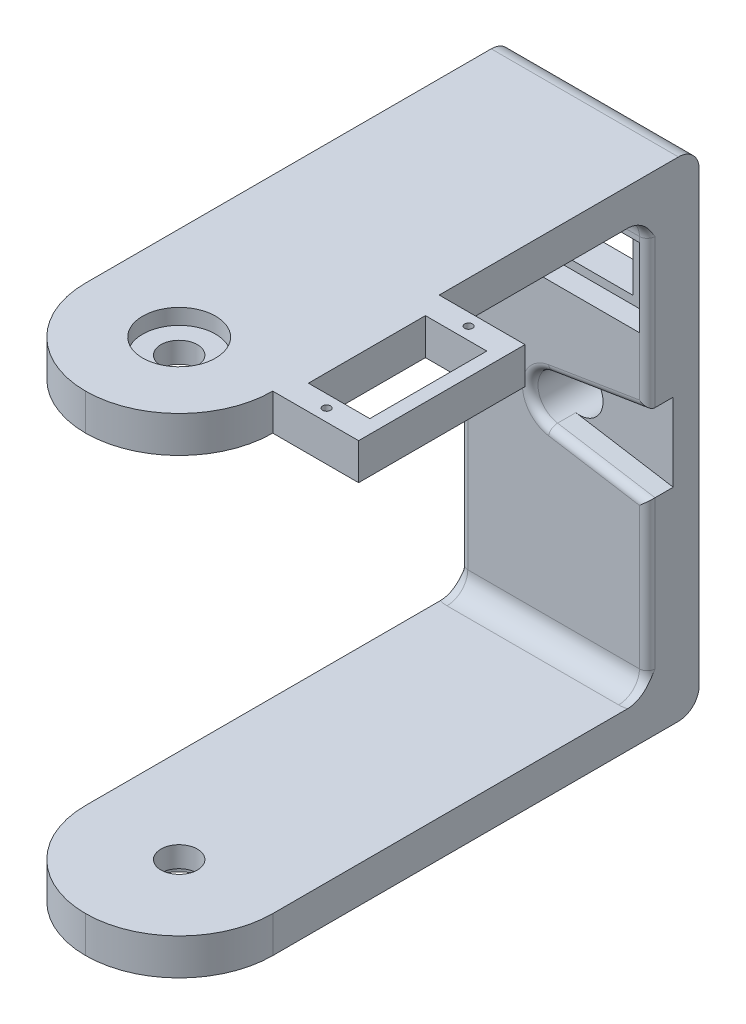
SolidWorks part; units mm, degrees
ref_plane "Front Plane" through (0, 0, 0) normal (1, 0, 0) x (0, 1, 0)
ref_plane "Top Plane" through (0, 0, 0) normal (0, 0, 1) x (0, 1, 0)
ref_plane "Right Plane" through (0, 0, 0) normal (0, 1, 0) x (-1, 0, 0)
sketch "Sketch1" plane through (0, 0, 0) normal (0, 0, 1) x (0, 1, 0)
  line L1 (-47, -18) -> (47, -18)
  line L2 (-47, -18) -> (-47, 18)
  line L3 (-47, 18) -> (47, 18)
  line L4 (47, -18) -> (47, 18)
  line L5 (-47, -18) -> (47, 18) construction
  line L6 (-47, 18) -> (47, -18) construction
  point P0 (0, 0)
  dimension "D1" = 94
  dimension "D2" = 36
extrude "Boss-Extrude1" add sketch "Sketch1" along normal blind 10
sketch "Sketch2" plane through (0, 0, 10) normal (0, 0, 1) x (1, 0, 0)
  line L0 (18, -47) -> (18, 47) construction
  line L1 (-18, 47) -> (18, 47)
  line L2 (-18, 47) -> (-18, 40)
  line L3 (-18, 40) -> (18, 40)
  line L4 (18, 47) -> (18, 40)
  line L6 (-18, -47) -> (18, -47)
  line L7 (-18, -47) -> (-18, -40)
  line L8 (-18, -40) -> (18, -40)
  line L9 (18, -47) -> (18, -40)
  dimension "D1" = 7
extrude "Boss-Extrude2" add sketch "Sketch2" along normal blind 90
sketch "Sketch3" plane through (0, -47, 0) normal (0, -1, 0) x (1, 0, 0)
  line L0 (-18, 82) -> (18, 82) construction
  line L1 (-18, 100) -> (-18, 0) construction
  line L2 (18, 100) -> (18, 0) construction
  line L3 (-18, 100) -> (18, 100) construction
  circle A0 centre (0, 82) radius 3.5
  dimension "D2" = 7
  dimension "D1" = 18
extrude "Cut-Extrude1" cut sketch "Sketch3" against normal through all both and the other way through all
sketch "Sketch4" plane through (0, -47, 0) normal (0, -1, 0) x (1, 0, 0)
  circle A0 centre (0, 82) radius 7
  dimension "D1" = 14
extrude "Cut-Extrude2" cut sketch "Sketch4" against normal blind 3 and the other way through all
sketch "Sketch5" plane through (0, 47, 0) normal (0, 1, 0) x (-1, 0, 0)
  circle A0 centre (0, 82) radius 7
  dimension "D1" = 14
extrude "Cut-Extrude3" cut sketch "Sketch5" against normal blind 3
fillet "Fillet1" radius 18 4 edges at (18, -43.5, 100) (-18, -43.5, 100) (18, 43.5, 100) (-18, 43.5, 100)
sketch "Sketch6" plane through (0, 0, 0) normal (0, 0, -1) x (1, 0, 0)
  circle A0 centre (0, 0) radius 7.5
  dimension "D1" = 15
extrude "Boss-Extrude3" add sketch "Sketch6" along normal blind 8
sketch "Sketch7" plane through (0, 0, -8) normal (0, 0, -1) x (1, 0, 0)
  circle A0 centre (0, 0) radius 4.5
  dimension "D1" = 9
extrude "Cut-Extrude4" cut sketch "Sketch7" against normal through all
fillet "Fillet2" radius 2 1 edges at (-7.5, 0, 0)
sketch "Sketch9" plane through (0, 0, 10) normal (0, 0, 1) x (1, 0, 0)
  line L0 (0, 0) -> (0, 40) construction
  line L1 (0, 27.4841) -> (18, 27.4841) construction
  line L2 (-11.25, 21.5841) -> (11.25, 21.5841)
  line L3 (-11.25, 21.5841) -> (-11.25, 33.3841)
  line L4 (-11.25, 33.3841) -> (11.25, 33.3841)
  line L5 (11.25, 21.5841) -> (11.25, 33.3841)
  line L6 (-11.25, 21.5841) -> (11.25, 33.3841) construction
  line L7 (-11.25, 33.3841) -> (11.25, 21.5841) construction
  line L8 (18, -40) -> (18, 40) construction
  line L9 (0, 27.4841) -> (-18, 27.4841) construction
  line L10 (-18, 40) -> (-18, -40) construction
  circle A1 centre (-13.65, 27.4841) radius 0.75
  circle A2 centre (13.65, 27.4841) radius 0.75
  circle A3 centre (-5.35, 27.4841) radius 5.9 construction
  point P4 (0, 27.4841)
  dimension "D5" = 1.5
  dimension "D1" = 22.5
  dimension "D2" = 11.8
  dimension "D3" = 28
  dimension "D4" = 13.65
  dimension "D6" = 13.65
extrude "Cut-Extrude5" cut sketch "Sketch9" against normal through all
sketch "Sketch10" plane through (0, 0, 10) normal (0, 0, 1) x (1, 0, 0)
  line L0 (-11.25, 27.4841) -> (11.25, 27.4841) construction
  line L1 (-11.25, 33.3841) -> (-11.25, 21.5841) construction
  line L2 (11.25, 21.5841) -> (11.25, 33.3841) construction
  line L4 (-16.5, 19.9841) -> (16.5, 19.9841)
  line L5 (-16.5, 19.9841) -> (-16.5, 34.9841)
  line L6 (-16.5, 34.9841) -> (16.5, 34.9841)
  line L7 (16.5, 19.9841) -> (16.5, 34.9841)
  line L8 (-16.5, 19.9841) -> (16.5, 34.9841) construction
  line L9 (-16.5, 34.9841) -> (16.5, 19.9841) construction
  point P6 (0, 27.4841)
  dimension "D1" = 15
  dimension "D2" = 33
extrude "Cut-Extrude6" cut sketch "Sketch10" against normal offset from surface (4 mm away) 6 up to face at (12.9, 27.4841, 0)
sketch "Sketch11" plane through (0, 47, 0) normal (0, 1, 0) x (-1, 0, 0)
  line L0 (-18, 82) -> (0, 82) construction
  line L1 (-26.0036, 82) -> (-26.0036, 50) construction
  line L2 (-17.5036, 82) -> (-34.5036, 82)
  line L3 (-17.5036, 82) -> (-17.5036, 50)
  line L4 (-17.5036, 50) -> (-34.5036, 50)
  line L5 (-34.5036, 82) -> (-34.5036, 50)
  line L6 (-34.5036, 66) -> (-26.0036, 66) construction
  line L7 (-31.9036, 54.75) -> (-20.1036, 54.75) construction
  line L8 (-31.9036, 54.75) -> (-31.9036, 77.25) construction
  line L9 (-31.9036, 77.25) -> (-20.1036, 77.25) construction
  line L10 (-20.1036, 54.75) -> (-20.1036, 77.25) construction
  line L11 (-31.9036, 54.75) -> (-20.1036, 77.25) construction
  line L12 (-31.9036, 77.25) -> (-20.1036, 54.75) construction
  circle A1 centre (-26.0036, 71.35) radius 5.9 construction
  circle A2 centre (0, 82) radius 21 construction
  circle A3 centre (-26.0036, 71.35) radius 7.1 construction
  point P10 (-26.0036, 66)
  dimension "D6" = 42
  dimension "D5" = 14.2
  dimension "D1" = 17
  dimension "D2" = 32
  dimension "D3" = 11.8
  dimension "D4" = 22.5
extrude "Boss-Extrude4" add sketch "Sketch11" against normal blind 7
sketch "Sketch12" plane through (0, 47, 0) normal (0, 1, 0) x (-1, 0, 0)
  line L0 (-34.5036, 66) -> (18, 66) construction
  line L1 (-34.5036, 82) -> (-34.5036, 50) construction
  line L2 (18, 82) -> (18, 0) construction
  line L3 (-18, 82) -> (-34.5036, 82) construction
  line L4 (-34.5036, 50) -> (-17.5036, 50) construction
  line L5 (-34.5036, 50) -> (-34.5036, 82) construction
  line L6 (-34.5036, 82) -> (-17.5036, 82) construction
  line L7 (-17.5036, 50) -> (-17.5036, 82) construction
  line L8 (-34.5036, 50) -> (-17.5036, 82) construction
  line L9 (-34.5036, 82) -> (-17.5036, 50) construction
  line L10 (-26.0036, 82) -> (-26.0036, 66) construction
  line L11 (-31.9036, 54.75) -> (-20.1036, 54.75)
  line L12 (-31.9036, 54.75) -> (-31.9036, 77.25)
  line L13 (-31.9036, 77.25) -> (-20.1036, 77.25)
  line L14 (-20.1036, 54.75) -> (-20.1036, 77.25)
  line L15 (-31.9036, 54.75) -> (-20.1036, 77.25) construction
  line L16 (-31.9036, 77.25) -> (-20.1036, 54.75) construction
  circle A0 centre (-26.0036, 79.65) radius 0.75
  circle A1 centre (-26.0036, 52.35) radius 0.75
  point P6 (-26.0036, 66)
  point P13 (-26.0036, 66)
  dimension "D4" = 1.5
  dimension "D1" = 17
  dimension "D2" = 11.8
  dimension "D3" = 22.5
  dimension "D5" = 13.65
extrude "Cut-Extrude7" cut sketch "Sketch12" against normal up to next
sketch "Sketch13" plane through (0, 0, 10) normal (0, 0, 1) x (1, 0, 0)
  line L1 (18, -7.5) -> (18, 7.5)
  line L4 (0, 0) -> (18, 0) construction
  line L5 (18, -40) -> (18, 40) construction
  line L6 (18, 7.5) -> (-0.7255, 4.4411)
  line L7 (-0.7255, -4.4411) -> (18, -7.5)
  circle A0 centre (0, 0) radius 4.5 construction
  arc A1 (-0.7255, 4.4411) -> (-0.7255, -4.4411) centre (0, 0) cw
  dimension "D1" = 15
extrude "Cut-Extrude8" cut sketch "Sketch13" against normal blind 5
fillet "Fillet3" radius 1.5 6 edges at (8.6373, -5.9706, 10) (-4.5, 0, 10) (8.6373, 5.9706, 10) (-18, 0, 10) (18, -23.75, 10) (18, 23.75, 10)
fillet "Fillet4" radius 4 8 edges at (17.5607, -40, 9.5607) (-17.5607, -40, 9.5607) (-17.5607, 40, 9.5607) (17.5607, 40, 9.5607) (0, -40, 10) (0, 40, 10) (0, -47, 0) (0, 47, 0)
